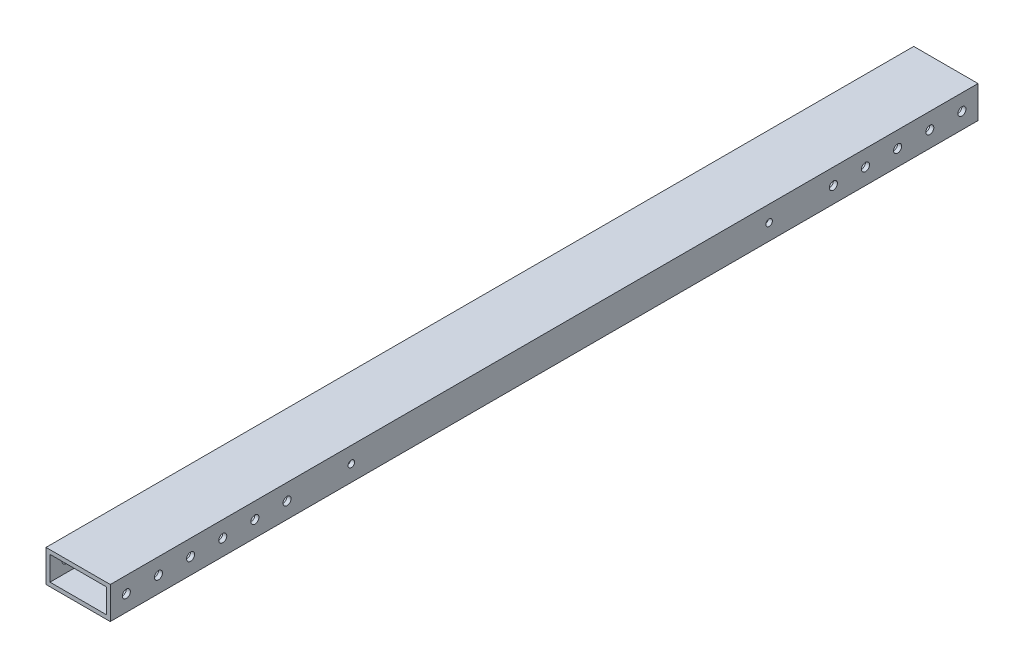
SolidWorks part; units mm, degrees
material "6061 Alloy"
ref_plane "Front Plane" through (0, 0, 0) normal (0, 0, 1) x (1, 0, 0)
ref_plane "Top Plane" through (0, 0, 0) normal (0, 1, 0) x (1, 0, 0)
ref_plane "Right Plane" through (0, 0, 0) normal (1, 0, 0) x (0, 0, -1)
sketch "Sketch1" plane through (0, 0, 0) normal (0, 0, 1) x (1, 0, 0)
  line L0 (-22.225, 9.525) -> (22.225, 9.525)
  line L2 (-25.4, 12.7) -> (25.4, 12.7)
  line L3 (-25.4, 12.7) -> (-25.4, -12.7)
  line L4 (-25.4, -12.7) -> (25.4, -12.7)
  line L5 (25.4, 12.7) -> (25.4, -12.7)
  line L10 (22.225, 9.525) -> (22.225, -9.525)
  line L11 (-22.225, -9.525) -> (22.225, -9.525)
  line L12 (-22.225, 9.525) -> (-22.225, -9.525)
  point P12 (0, 12.7)
  point P14 (25.4, 0)
  dimension "Wall Thickness" = 3.175
  dimension "Outside Width" = 50.8
  dimension "Outside Height" = 25.4
  dimension "Inside Height" = 19.05
  dimension "Inside Width" = 44.45
sketch "Sketch2" plane through (0, 0, 0) normal (1, 0, 0) x (0, 0, -1)
  line L0 (342.9, 0) -> (-342.9, 0)
  point P4 (0, 0)
  point P7 (-342.9, 0)
  point P10 (342.9, 0)
  dimension "Length" = 685.8
sketch "Sketch3" plane through (0, 0, 0) normal (0, 0, 1) x (1, 0, 0)
  line L21 (25.4, 12.7) -> (-25.4, 12.7)
  line L22 (25.4, -12.7) -> (25.4, 12.7)
  line L23 (-25.4, -12.7) -> (25.4, -12.7)
  line L24 (-25.4, 12.7) -> (-25.4, -12.7)
  line L25 (25.4, 12.7) -> (-25.4, 12.7)
  line L26 (25.4, -12.7) -> (25.4, 12.7)
  line L27 (-25.4, -12.7) -> (25.4, -12.7)
  line L28 (-25.4, 12.7) -> (-25.4, -12.7)
  line L29 (22.225, 9.525) -> (-22.225, 9.525)
  line L30 (22.225, -9.525) -> (22.225, 9.525)
  line L31 (-22.225, -9.525) -> (22.225, -9.525)
  line L32 (-22.225, 9.525) -> (-22.225, -9.525)
  line L33 (22.225, 9.525) -> (-22.225, 9.525)
  line L34 (22.225, -9.525) -> (22.225, 9.525)
  line L35 (-22.225, -9.525) -> (22.225, -9.525)
  line L36 (-22.225, 9.525) -> (-22.225, -9.525)
  dimension "D1" = 0
  dimension "D2" = 0
extrude "Boss-Extrude1" add sketch "Sketch3" along normal up to vertex (342.9 mm away) and the other way up to vertex (342.9 mm away) up to point (0, 0, 342.9) other way up to point (0, 0, -342.9)
sketch "Drawing Reference" plane through (0, 0, 0) normal (1, 0, 0) x (0, 0, -1)
  line L0 (-342.9, 0) -> (342.9, 0) construction
  line L1 (0, -12.7) -> (0, 12.7) construction
  line L2 (-342.9, -12.7) -> (342.9, -12.7) construction
  line L5 (-342.9, 12.7) -> (342.9, 12.7) construction
  point P7 (-306.324, 0)
  point P8 (306.324, 0)
  dimension "D1" = 36.576
sketch "Sketch5" plane through (25.4, 0, 0) normal (1, 0, 0) x (0, 0, -1)
  line L0 (-342.9, 0) -> (-279.4, 0)
  line L1 (-342.9, -12.7) -> (-342.9, 12.7) construction
  line L2 (-279.4, 0) -> (-254, 0)
  line L3 (-254, 0) -> (-228.6, 0)
  line L4 (-228.6, 0) -> (-203.2, 0)
  point P5 (0, 0)
sketch "Sketch8" plane through (25.4, 0, 0) normal (1, 0, 0) x (0, 0, -1)
  line L0 (342.9, 0) -> (304.8, 0)
  line L1 (342.9, -12.7) -> (342.9, 12.7) construction
  line L2 (304.8, 0) -> (279.4, 0)
  line L3 (279.4, 0) -> (254, 0)
  line L4 (254, 0) -> (228.6, 0)
  line L5 (342.9, 0) -> (330.2, 0)
hole_wizard "1/4 (0.25) Diameter Hole3" positions "Sketch12" profile "Sketch13" hole size "1/4" standard "ANSI Inch" end condition through all
sketch "Sketch12" plane through (-25.4, 0, 0) normal (-1, 0, 0) x (0, 0, 1)
  point P4 (-330.2, 0)
sketch "Sketch13" plane through (-25.4, 0, -330.2) normal (0, 1, 0) x (0, 0, 1)
  line L0 (0, 0) -> (0, 50.8)
  line L1 (0, 50.8) -> (3.175, 50.8)
  line L2 (3.175, 50.8) -> (3.175, 0)
  line L5 (3.175, 0) -> (0, 0)
  line L11 (0, -6.35) -> (0, 107.95) construction
  dimension "Thru Hole Dia." = 6.35
  dimension "Thru Hole Depth" = 50.8
hole_wizard "1/4 (0.25) Diameter Hole4" positions "Sketch14" profile "Sketch15" hole size "1/4" standard "ANSI Inch" end condition through all
sketch "Sketch14" plane through (-25.4, 0, 0) normal (-1, 0, 0) x (0, 0, 1)
  point P0 (304.8, 0)
  point P3 (330.2, 0)
sketch "Sketch15" plane through (-25.4, 0, 304.8) normal (0, 1, 0) x (0, 0, 1)
  line L0 (0, 0) -> (0, 50.8)
  line L1 (0, 50.8) -> (3.175, 50.8)
  line L2 (3.175, 50.8) -> (3.175, 0)
  line L5 (3.175, 0) -> (0, 0)
  line L11 (0, -6.35) -> (0, 107.95) construction
  dimension "Thru Hole Dia." = 6.35
  dimension "Thru Hole Depth" = 50.8
hole_wizard "1/4 (0.25) Diameter Hole5" positions "Sketch17" profile "Sketch18" hole size "1/4" standard "ANSI Inch" end condition through all
sketch "Sketch17" plane through (25.4, 0, 0) normal (1, 0, 0) x (0, 0, -1)
  point P0 (304.8, 0)
  point P3 (279.4, 0)
sketch "Sketch18" plane through (25.4, 0, -304.8) normal (0, 1, 0) x (0, 0, -1)
  line L0 (0, 0) -> (0, 50.8)
  line L1 (0, 50.8) -> (3.175, 50.8)
  line L2 (3.175, 50.8) -> (3.175, 0)
  line L5 (3.175, 0) -> (0, 0)
  line L11 (0, -6.35) -> (0, 107.95) construction
  dimension "Thru Hole Dia." = 6.35
  dimension "Thru Hole Depth" = 50.8
hole_wizard "1/4 (0.25) Diameter Hole6" positions "Sketch19" profile "Sketch20" hole size "1/4" standard "ANSI Inch" end condition through all
sketch "Sketch19" plane through (25.4, 0, 0) normal (1, 0, 0) x (0, 0, -1)
  point P0 (228.6, 0)
  point P3 (254, 0)
sketch "Sketch20" plane through (25.4, 0, -228.6) normal (0, 1, 0) x (0, 0, -1)
  line L0 (0, 0) -> (0, 50.8)
  line L1 (0, 50.8) -> (3.175, 50.8)
  line L2 (3.175, 50.8) -> (3.175, 0)
  line L5 (3.175, 0) -> (0, 0)
  line L11 (0, -6.35) -> (0, 107.95) construction
  dimension "Thru Hole Dia." = 6.35
  dimension "Thru Hole Depth" = 50.8
hole_wizard "1/4 (0.25) Diameter Hole7" positions "Sketch21" profile "Sketch22" hole size "1/4" standard "ANSI Inch" end condition through all
sketch "Sketch21" plane through (25.4, 0, 0) normal (1, 0, 0) x (0, 0, -1)
  point P0 (-203.2, 0)
  point P3 (-228.6, 0)
sketch "Sketch22" plane through (25.4, 0, 203.2) normal (0, 1, 0) x (0, 0, -1)
  line L0 (0, 0) -> (0, 50.8)
  line L1 (0, 50.8) -> (3.175, 50.8)
  line L2 (3.175, 50.8) -> (3.175, 0)
  line L5 (3.175, 0) -> (0, 0)
  line L11 (0, -6.35) -> (0, 107.95) construction
  dimension "Thru Hole Dia." = 6.35
  dimension "Thru Hole Depth" = 50.8
hole_wizard "1/4 (0.25) Diameter Hole8" positions "Sketch23" profile "Sketch24" hole size "1/4" standard "ANSI Inch" end condition through all
sketch "Sketch23" plane through (25.4, 0, 0) normal (1, 0, 0) x (0, 0, -1)
  point P0 (-279.4, 0)
  point P3 (-254, 0)
sketch "Sketch24" plane through (25.4, 0, 279.4) normal (0, 1, 0) x (0, 0, -1)
  line L0 (0, 0) -> (0, 50.8)
  line L1 (0, 50.8) -> (3.175, 50.8)
  line L2 (3.175, 50.8) -> (3.175, 0)
  line L5 (3.175, 0) -> (0, 0)
  line L11 (0, -6.35) -> (0, 107.95) construction
  dimension "Thru Hole Dia." = 6.35
  dimension "Thru Hole Depth" = 50.8
sketch "Sketch25" plane through (25.4, 0, 0) normal (1, 0, 0) x (0, 0, -1)
  line L0 (-203.2, 0) -> (-152.4, 0)
  line L1 (228.6, 0) -> (177.8, 0)
  point P7 (0, 0)
hole_wizard "13/64 (0.20313) Diameter Hole1" positions "Sketch26" profile "Sketch27" hole size "13/64" standard "ANSI Inch" end condition through all
sketch "Sketch26" plane through (25.4, 0, 0) normal (1, 0, 0) x (0, 0, -1)
  point P0 (-152.4, 0)
  point P3 (177.8, 0)
sketch "Sketch27" plane through (25.4, 0, 152.4) normal (0, 1, 0) x (0, 0, -1)
  line L0 (0, 0) -> (0, 50.8)
  line L1 (0, 50.8) -> (2.5798, 50.8)
  line L2 (2.5798, 50.8) -> (2.5798, 0)
  line L5 (2.5798, 0) -> (0, 0)
  line L11 (0, -6.35) -> (0, 107.95) construction
  dimension "Thru Hole Dia." = 5.1595
  dimension "Thru Hole Depth" = 50.8
sketch "Sketch28" plane through (-25.4, 0, 0) normal (-1, 0, 0) x (0, 0, 1)
  line L0 (102.8316, 0) -> (77.4316, 0)
  line L1 (-103.5434, 0) -> (-128.9434, 0)
hole_wizard "1/2 (0.5) Diameter Hole1" positions "Sketch29" profile "Sketch30" hole size "1/2" standard "ANSI Inch"
sketch "Sketch29" plane through (-25.4, 0, 0) normal (-1, 0, 0) x (0, 0, 1)
  point P1 (-591.3016, -480.8022)
  point P3 (-103.5434, 0)
  point P6 (77.4316, 0)
  point P9 (102.8316, 0)
  point P13 (-128.9434, 0)
sketch "Sketch30" plane through (-25.4, -480.8022, -591.3016) normal (0, 1, 0) x (0, 0, 1)
  line L0 (0, 0) -> (0, 10.1655)
  line L1 (0, 10.1655) -> (6.35, 6.35)
  line L2 (6.35, 6.35) -> (6.35, 0)
  line L5 (6.35, 0) -> (0, 0)
  line L10 (0, 10.1655) -> (-6.35, 6.35) construction
  line L11 (0, -6.35) -> (0, 107.95) construction
  dimension "Hole Dia." = 12.7
  dimension "Hole Depth" = 6.35
  dimension "Drill Angle" = 118
equation "\"D1@Drawing Reference\"=\"Outside Width@Sketch1\" * 0.72"
